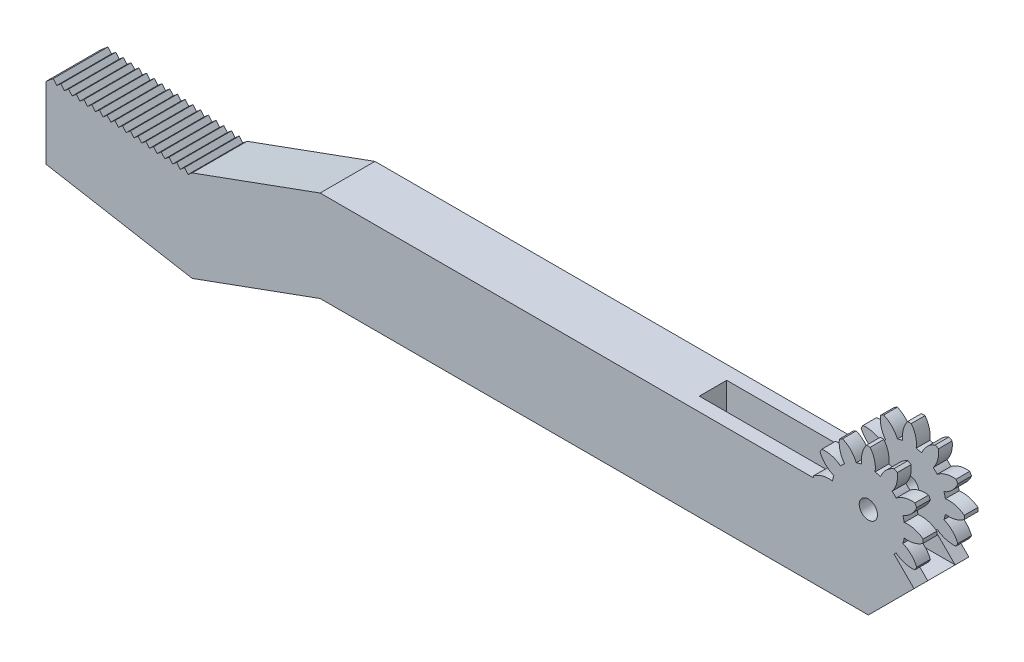
SolidWorks part; units mm, degrees
note: The reader was unsure of these and kept them because the rebuilt part matched: shared geometry of "Sketch3<6>".
ref_plane "Front Plane" through (0, 0, 0) normal (1, 0, 0) x (0, 1, 0)
ref_plane "Top Plane" through (0, 0, 0) normal (0, 0, 1) x (0, 1, 0)
ref_plane "Right Plane" through (0, 0, 0) normal (0, 1, 0) x (-1, 0, 0)
sketch "Sketch1" plane through (0, 0, 0) normal (0, 0, 1) x (0, 1, 0)
  line L0 (0, 0) -> (0, 300)
  line L1 (0, 300) -> (-25.4779, 370)
  line L2 (-25.4779, 370) -> (-27.4063, 372.2981)
  line L3 (-27.4063, 372.2981) -> (-25.1081, 374.2265)
  line L4 (-25.1081, 374.2265) -> (-27.0365, 376.5246)
  line L5 (-27.0365, 376.5246) -> (-24.7384, 378.453)
  line L6 (-24.3686, 382.6795) -> (-26.297, 384.9776)
  line L7 (-24.7384, 378.453) -> (-26.6667, 380.7511)
  line L8 (-26.6667, 380.7511) -> (-24.3686, 382.6795)
  line L9 (-26.297, 384.9776) -> (-23.9988, 386.906)
  line L10 (-23.9988, 386.906) -> (-25.9272, 389.2041)
  line L11 (-25.9272, 389.2041) -> (-23.6291, 391.1325)
  line L12 (-23.6291, 391.1325) -> (-25.5574, 393.4306)
  line L13 (-25.5574, 393.4306) -> (-23.2593, 395.359)
  line L14 (-22.8895, 399.5855) -> (-24.8179, 401.8836)
  line L15 (-23.2593, 395.359) -> (-25.1877, 397.6571)
  line L16 (-25.1877, 397.6571) -> (-22.8895, 399.5855)
  line L17 (-24.8179, 401.8836) -> (-22.5198, 403.812)
  line L18 (-22.5198, 403.812) -> (-24.4481, 406.1101)
  line L19 (-24.4481, 406.1101) -> (-22.15, 408.0385)
  line L20 (-22.15, 408.0385) -> (-24.0783, 410.3366)
  line L21 (-24.0783, 410.3366) -> (-21.7802, 412.265)
  line L22 (-21.7802, 412.265) -> (-23.7086, 414.5631)
  line L23 (-23.7086, 414.5631) -> (-21.4104, 416.4915)
  line L24 (-21.0407, 420.718) -> (-22.969, 423.0161)
  line L25 (-21.4104, 416.4915) -> (-23.3388, 418.7896)
  line L26 (-23.3388, 418.7896) -> (-21.0407, 420.718)
  line L27 (-22.969, 423.0161) -> (-20.6709, 424.9445)
  line L28 (-20.6709, 424.9445) -> (-22.5993, 427.2426)
  line L29 (-22.5993, 427.2426) -> (-20.3011, 429.1709)
  line L30 (-20.3011, 429.1709) -> (-22.2295, 431.4691)
  line L31 (-22.2295, 431.4691) -> (-19.9314, 433.3974)
  line L32 (-19.5616, 437.6239) -> (-21.49, 439.9221)
  line L33 (-19.9314, 433.3974) -> (-21.8597, 435.6956)
  line L34 (-21.8597, 435.6956) -> (-19.5616, 437.6239)
  line L35 (-21.49, 439.9221) -> (-19.1918, 441.8504)
  line L36 (-19.1918, 441.8504) -> (-21.1202, 444.1486)
  line L37 (-21.1202, 444.1486) -> (-18.822, 446.0769)
  line L38 (-18.822, 446.0769) -> (-22.1139, 450)
  line L40 (-22.1139, 450) -> (-61.3718, 450)
  line L41 (-61.3718, 450) -> (-75.4779, 370)
  line L42 (-75.4779, 370) -> (-50, 300)
  line L43 (-50, 300) -> (-50, 0)
  line L45 (-50, 0) -> (-25, -25)
  line L46 (-25, -25) -> (0, 0)
  dimension "D1" = 3
  dimension "D2" = 300
  dimension "D3" = 200
  dimension "D4" = 70
  dimension "D5" = 160
  dimension "D6" = 50
  dimension "D7" = 25
  dimension "D8" = 450
  dimension "D10" = 150
extrude "Boss-Extrude1" add sketch "Sketch1" along normal blind 30
sketch "Sketch3" plane through (0, 0, 30) normal (0, 0, 1) x (1, 0, 0)
  line L3 (0, 0) -> (0, 30) construction
  line L4 (15.1799, -13.0219) -> (14.1009, -14.1009)
  line L5 (25, -25) -> (0, 0) construction
  line L6 (14.1009, -14.1009) -> (3.5355, -3.5355)
  line L8 (-5, 0) -> (-30, 0)
  circle A27 centre (0, 0) radius 5
  circle A28 centre (0, 0) radius 30 construction
  arc A29 (-0.9999, 29.9833) -> (0.9999, 29.9833) centre (0, 0) cw
  arc A31 (14.1258, 26.4663) -> (6.6353, 18.8673) centre (19.4641, 13.7128) ccw
  arc A32 (-18.8673, 6.6353) -> (-19.6572, 3.6873) centre (0, 0) ccw
  arc A33 (15.8576, 25.4664) -> (13.0219, 15.1799) centre (2.1436, 23.7128) cw
  arc A34 (-0.9999, 29.9833) -> (-3.6873, 19.6572) centre (10, 21.6077) ccw
  arc A35 (0.9999, 29.9833) -> (3.6873, 19.6572) centre (-10, 21.6077) cw
  arc A48 (14.1258, 26.4663) -> (15.8576, 25.4664) centre (0, 0) cw
  arc A83 (25.4664, 15.8576) -> (15.1799, 13.0219) centre (23.7128, 2.1436) ccw
  arc A84 (26.4663, 14.1258) -> (18.8673, 6.6353) centre (13.7128, 19.4641) cw
  arc A85 (25.4664, 15.8576) -> (26.4663, 14.1258) centre (0, 0) cw
  arc A86 (29.9833, 0.9999) -> (19.6572, 3.6873) centre (21.6077, -10) ccw
  arc A87 (29.9833, -0.9999) -> (19.6572, -3.6873) centre (21.6077, 10) cw
  arc A88 (29.9833, 0.9999) -> (29.9833, -0.9999) centre (0, 0) cw
  arc A89 (26.4663, -14.1258) -> (18.8673, -6.6353) centre (13.7128, -19.4641) ccw
  arc A90 (25.4664, -15.8576) -> (15.1799, -13.0219) centre (23.7128, -2.1436) cw
  arc A91 (26.4663, -14.1258) -> (25.4664, -15.8576) centre (0, 0) cw
  arc A92 (-15.1799, 13.0219) -> (-13.0219, 15.1799) centre (0, 0) cw
  arc A94 (15.8576, -25.4664) -> (14.1258, -26.4663) centre (0, 0) cw
  arc A97 (0.9999, -29.9833) -> (-0.9999, -29.9833) centre (0, 0) cw
  arc A100 (-14.1258, -26.4663) -> (-15.8576, -25.4664) centre (0, 0) cw
  arc A103 (-25.4664, -15.8576) -> (-26.4663, -14.1258) centre (0, 0) cw
  arc A105 (-29.9833, 0.9999) -> (-19.6572, 3.6873) centre (-21.6077, -10) cw
  arc A106 (-29.9833, -0.9999) -> (-29.9833, 0.9999) centre (0, 0) cw
  arc A107 (-26.4663, 14.1258) -> (-18.8673, 6.6353) centre (-13.7128, 19.4641) ccw
  arc A108 (-25.4664, 15.8576) -> (-15.1799, 13.0219) centre (-23.7128, 2.1436) cw
  arc A109 (-26.4663, 14.1258) -> (-25.4664, 15.8576) centre (0, 0) cw
  arc A110 (-15.8576, 25.4664) -> (-13.0219, 15.1799) centre (-2.1436, 23.7128) ccw
  arc A111 (-14.1258, 26.4663) -> (-6.6353, 18.8673) centre (-19.4641, 13.7128) cw
  arc A112 (-15.8576, 25.4664) -> (-14.1258, 26.4663) centre (0, 0) cw
  arc A113 (-3.6873, 19.6572) -> (-6.6353, 18.8673) centre (0, 0) ccw
  arc A114 (6.6353, 18.8673) -> (3.6873, 19.6572) centre (0, 0) ccw
  arc A115 (15.1799, 13.0219) -> (13.0219, 15.1799) centre (0, 0) ccw
  arc A116 (19.6572, 3.6873) -> (18.8673, 6.6353) centre (0, 0) ccw
  arc A117 (18.8673, -6.6353) -> (19.6572, -3.6873) centre (0, 0) ccw
  arc A118 (15.8576, -25.4664) -> (13.0219, -15.1799) centre (2.1436, -23.7128) ccw [skipped]
  arc A119 (14.1258, -26.4663) -> (6.6353, -18.8673) centre (19.4641, -13.7128) cw [skipped]
  arc A120 (0.9999, -29.9833) -> (3.6873, -19.6572) centre (-10, -21.6077) ccw [skipped]
  arc A121 (-0.9999, -29.9833) -> (-3.6873, -19.6572) centre (10, -21.6077) cw [skipped]
  arc A122 (-14.1258, -26.4663) -> (-6.6353, -18.8673) centre (-19.4641, -13.7128) ccw [skipped]
  arc A123 (-15.8576, -25.4664) -> (-13.0219, -15.1799) centre (-2.1436, -23.7128) cw [skipped]
  arc A124 (-25.4664, -15.8576) -> (-15.1799, -13.0219) centre (-23.7128, -2.1436) ccw [skipped]
  arc A125 (-26.4663, -14.1258) -> (-18.8673, -6.6353) centre (-13.7128, -19.4641) cw [skipped]
  arc A126 (-29.9833, -0.9999) -> (-19.6572, -3.6873) centre (-21.6077, 10) ccw [skipped]
  point P83 (0, 0)
  point P101 (0, 0)
  line M59 (25, -25) -> (0, 0)
  line M60 (0, 0) -> (-300, 0)
  dimension "D1" = 60
  dimension "D2" = 10
  dimension "D3" = 40
  dimension "D6" = 10
  dimension "D4" = 1
  dimension "D5" = 3.6873
  dimension "D7" = 20
extrude "Boss-Extrude2" add sketch "Sketch3" against normal blind 30
extrude "Cut-Extrude1" cut sketch "Sketch3<6>" against normal blind 30 contours A27 M60 M59
sketch "Sketch3<6>" plane through (0, 0, 30) normal (0, 0, 1) x (1, 0, 0) same geometry as "Sketch3"
sketch "Sketch4" plane through (0, 0, 0) normal (1, 0, 0) x (0, 1, 0)
  line L0 (-25, 7.5) -> (-25, 22.5)
  line L1 (-25, 22.5) -> (49, 22.5)
  line L2 (-110.9173, 22.2439) -> (-110.9173, 7.7561)
  line L3 (-25, 7.5) -> (49, 7.5)
  line L4 (49, 22.5) -> (49, 7.5)
  line L7 (-25, 30) -> (-25, 0) construction
  dimension "D1" = 15
  dimension "D2" = 7.5
  dimension "D3" = 74
extrude "Cut-Extrude3" cut sketch "Sketch4" along normal blind 43 and the other way blind 100 contours L1 L4 L3 L0
